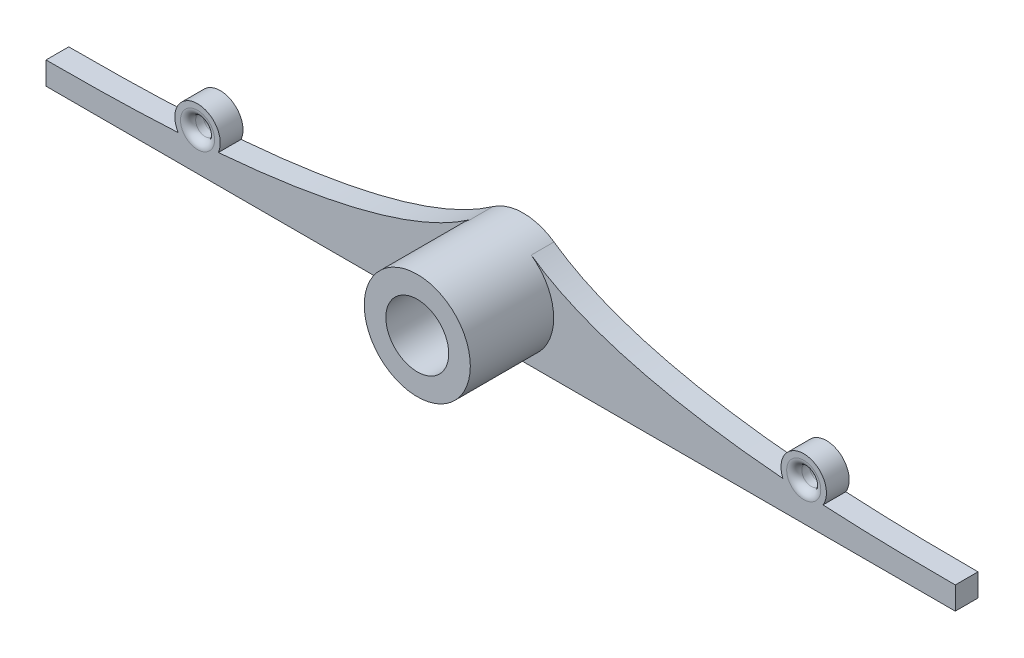
SolidWorks part; units mm, degrees
ref_plane "Front Plane" through (0, 0, 0) normal (0, 0, 1) x (1, 0, 0)
ref_plane "Top Plane" through (0, 0, 0) normal (0, 1, 0) x (1, 0, 0)
ref_plane "Right Plane" through (0, 0, 0) normal (1, 0, 0) x (0, 0, -1)
sketch "Sketch1" plane through (0, 0, 0) normal (0, 0, 1) x (1, 0, 0)
  line L0 (60, -7) -> (-60, -7)
  line L1 (-60, -7) -> (-60, -4)
  line L2 (-60, -4) -> (60, -4)
  line L3 (60, -4) -> (60, -7)
  line L4 (0, -1000) -> (0, 49000) construction
  circle A0 centre (0, 0) radius 4.15
  circle A1 centre (0, 0) radius 7
  circle A2 centre (-40, -2) radius 1.25
  circle A3 centre (-40, -2) radius 3
  circle A4 centre (40, -2) radius 1.25
  circle A5 centre (40, -2) radius 3
  spline S0 degree 3 poles (-60, -4) (-44.811, -4) (-17.0644, -3.4836) (-4.0387, 5.7175) knots 0 0 0 0 1 1 1 1
  spline S1 degree 3 poles (60, -4) (44.811, -4) (17.0644, -3.4836) (4.0387, 5.7175) knots 0 0 0 0 1 1 1 1
  point P6 (0, -7)
  point P15 (0, 0)
  dimension "D1" = 8.3
  dimension "D2" = 14
  dimension "D5" = 2.5
  dimension "D6" = 6
  dimension "D3" = 3
  dimension "D4" = 2
  dimension "D7" = 120
  dimension "D8" = 20
  dimension "D9" = 20
extrude "Boss-Extrude1" add sketch "Sketch1" along normal blind 3 contours A1 L2 L1 L0 | A1 L0 L3 L2 | S0 L2 A1 | L2 S1 A1 | A3 S0 A2 | S0 A3 L2 | L2 A3 | S0 L2 A3 | L2 A5 | A5 S1 L2 | S1 A5 A4 | L2 S1 A5 region at (31.8496, -5.5407, 0) region at (-31.8496, -5.5407, 0) region at (46.5151, -3.8764, 0) region at (-16.6955, -1.6554, 0) region at (16.6955, -1.6554, 0) region at (40, -4.4063, 0) region at (39.7036, -3.6863, 0) region at (39.9067, -3.337, 0) region at (-46.5151, -3.8764, 0) region at (-40, -4.4063, 0) region at (-39.7036, -3.6863, 0) region at (-40.8003, 0.8129, 0)
extrude "Boss-Extrude2" add sketch "Sketch1<3>" along normal blind 14 contours L4 A0 L2 A1 | L4 A1 L2 A0 | A1 L4 A0 L2 | A0 L4 A1 L2 region at (-2.2495, -5.236, 0) region at (2.2495, -5.236, 0) region at (-4.0614, 1.6539, 0) region at (4.0614, 1.6539, 0)
sketch "Sketch1<3>" plane through (0, 0, 0) normal (0, 0, 1) x (1, 0, 0) same geometry as "Sketch1"
fillet "Fillet1" radius 1 4 edges at (41.25, -2, 3) (41.25, -2, 0) (-38.75, -2, 0) (-38.75, -2, 3)
